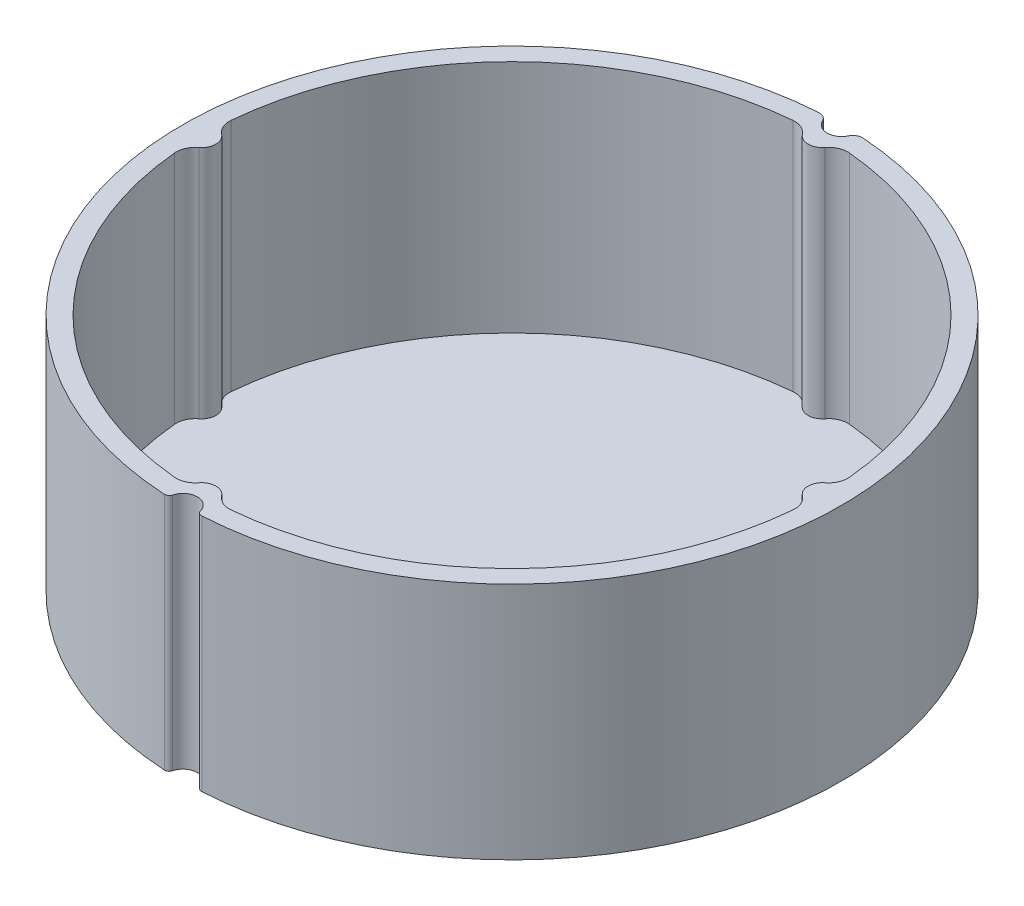
SolidWorks part; units mm, degrees
ref_plane "Front Plane" through (0, 0, 0) normal (0, 0, 1) x (1, 0, 0)
ref_plane "Top Plane" through (0, 0, 0) normal (0, 1, 0) x (1, 0, 0)
ref_plane "Right Plane" through (0, 0, 0) normal (1, 0, 0) x (0, 0, -1)
sketch "Sketch1" plane through (0, 0, 0) normal (0, 1, 0) x (1, 0, 0)
  line L3 (0, 0.002) -> (0, 3.7877) construction
  line L4 (0, 3.7877) -> (2.417, 3.7877)
  line L5 (0, 3.7877) -> (-2.417, 3.7877)
  arc A0 (1.9642, -34.442) -> (34.1982, 4.5552) centre (0, 0.002) ccw
  arc A2 (-2.417, 3.7877) -> (2.417, 3.7877) centre (0, 0.002) ccw
  circle A3 centre (0, 0.002) radius 34.5 construction
  arc A7 (-1.3541, 33.8562) -> (1.3541, 33.8562) centre (0, 34.5015) ccw
  arc A8 (34.1982, 4.5552) -> (2.3241, 34.4236) centre (0, 0.002) ccw
  arc A9 (-2.3241, 34.4236) -> (-34.1982, 4.5552) centre (0, 0.002) ccw
  arc A10 (-34.1982, 4.5552) -> (-1.9642, -34.442) centre (0, 0.002) ccw
  arc A11 (1.3541, 33.8562) -> (2.3241, 34.4236) centre (2.2568, 33.4259) cw
  arc A12 (-1.3541, 33.8562) -> (-2.3241, 34.4236) centre (-2.2568, 33.4259) ccw
  arc A13 (1.4518, -34.0686) -> (-1.4518, -34.0686) centre (0, -34.4457) ccw
  arc A14 (1.4518, -34.0686) -> (1.9642, -34.442) centre (1.9358, -33.9428) ccw
  arc A15 (-1.4518, -34.0686) -> (-1.9642, -34.442) centre (-1.9358, -33.9428) cw
  point P15 (1.4997, 34.4694)
  dimension "D2" = 4.834
  dimension "D3" = 4.4915
  dimension "D4" = 34.5
  dimension "D5" = 1
  dimension "D6" = 1.5
  dimension "D7" = 0.5
  dimension "D11" = 1.4997
sketch "Sketch2" plane through (0, 0, 0) normal (0, 1, 0) x (1, 0, 0)
  arc A0 (-32.3648, -2.9619) -> (-2.9619, -32.3648) centre (0, 0) ccw
  arc A1 (-1.1913, 31.5885) -> (1.1913, 31.5885) centre (0, 32.5) ccw
  arc A2 (31.5885, 1.1913) -> (31.5885, -1.1913) centre (32.5, 0) ccw
  arc A3 (1.1913, -31.5885) -> (-1.1913, -31.5885) centre (0, -32.5) ccw
  arc A4 (-31.5885, -1.1913) -> (-31.5885, 1.1913) centre (-32.5, 0) ccw
  arc A5 (-2.9619, 32.3648) -> (-32.3648, 2.9619) centre (0, 0) ccw
  arc A6 (32.3648, 2.9619) -> (2.9619, 32.3648) centre (0, 0) ccw
  arc A7 (2.9619, -32.3648) -> (32.3648, -2.9619) centre (0, 0) ccw
  arc A8 (-31.5885, -1.1913) -> (-32.3648, -2.9619) centre (-30.3731, -2.7796) ccw
  arc A9 (-31.5885, 1.1913) -> (-32.3648, 2.9619) centre (-30.3731, 2.7796) cw
  arc A10 (1.1913, -31.5885) -> (2.9619, -32.3648) centre (2.7796, -30.3731) ccw
  arc A11 (-1.1913, -31.5885) -> (-2.9619, -32.3648) centre (-2.7796, -30.3731) cw
  arc A12 (31.5885, 1.1913) -> (32.3648, 2.9619) centre (30.3731, 2.7796) ccw
  arc A13 (31.5885, -1.1913) -> (32.3648, -2.9619) centre (30.3731, -2.7796) cw
  arc A14 (1.1913, 31.5885) -> (2.9619, 32.3648) centre (2.7796, 30.3731) cw
  arc A15 (-1.1913, 31.5885) -> (-2.9619, 32.3648) centre (-2.7796, 30.3731) ccw
  point P21 (1.4996, -32.4654)
  point P26 (32.4654, 1.4996)
  point P33 (-1.4996, 32.4654)
  dimension "D1" = 32.5
  dimension "D2" = 1.5
  dimension "D3" = 1.5
  dimension "D4" = 1.5
  dimension "D5" = 1.5
  dimension "D6" = 2
extrude "Boss-Extrude1" add sketch "Sketch1" along normal blind 25 contours A10 A0 A8 A7 A9 A2 L5 L4 region at (2.2155, 0, 33.5591)
extrude "Cut-Extrude2" cut sketch "Sketch2" along normal through all
extrude "Boss-Extrude2" add sketch "Sketch2<2>" along normal blind 0.4
sketch "Sketch2<2>" plane through (0, 0, 0) normal (0, 1, 0) x (1, 0, 0) same geometry as "Sketch2"
